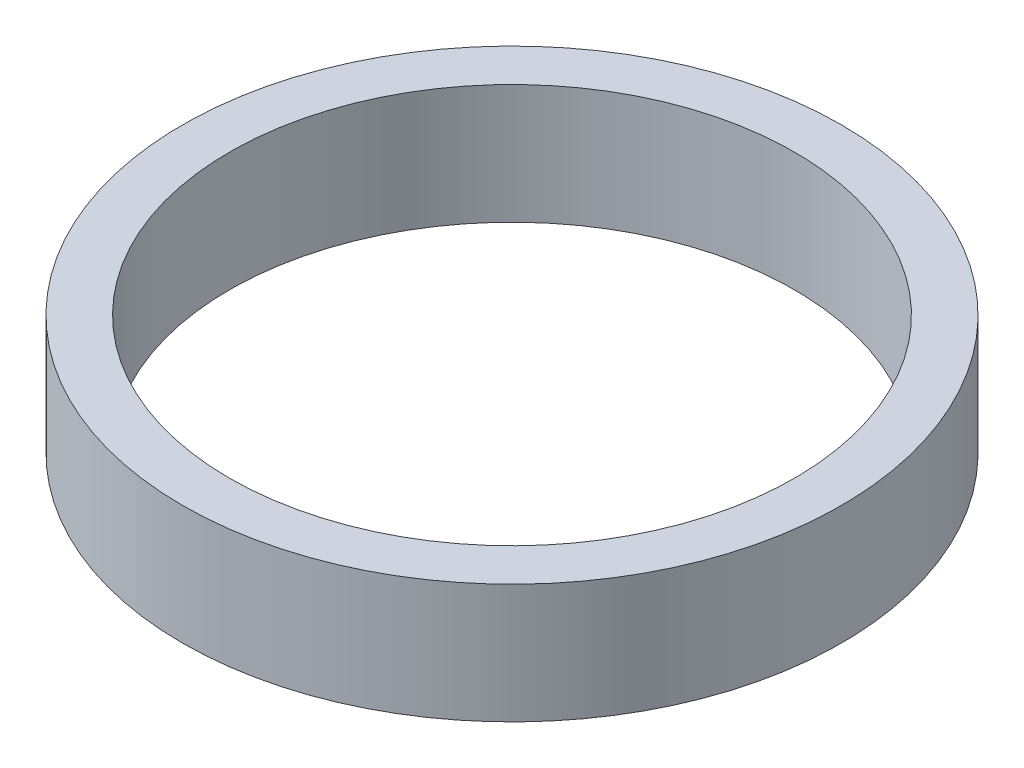
SolidWorks part; units mm, degrees
ref_plane "Front Plane" through (0, 0, 0) normal (0, 0, 1) x (1, 0, 0)
ref_plane "Top Plane" through (0, 0, 0) normal (0, 1, 0) x (1, 0, 0)
ref_plane "Right Plane" through (0, 0, 0) normal (1, 0, 0) x (0, 0, -1)
sketch "Sketch1" plane through (0, 0, 0) normal (0, 1, 0) x (1, 0, 0)
  circle A0 centre (0, 0) radius 52.5
  dimension "FLANGE_OD" = 105
extrude "Boss-Extrude1" add sketch "Sketch1" along normal blind 19
sketch "Sketch2" plane through (0, 0, 0) normal (0, 1, 0) x (1, 0, 0)
  circle A0 centre (0, 0) radius 45
  dimension "BORE_D" = 90
extrude "Cut-Extrude1" cut sketch "Sketch2" along normal through all
sketch "Sketch3" plane through (0, 19, 0) normal (0, 1, 0) x (1, 0, 0)
  circle A0 centre (0, 0) radius 24.4007 construction
  circle A1 centre (-24.4007, 0) radius 1.5
  dimension "BOLT_D" = 3
  dimension "BOLT_PCD" = 48.8014
extrude "Cut-Extrude2" cut sketch "Sketch3" against normal blind 13.1651 rebuild error yes
pattern_circular "CirPattern1" count 3 over 360 rebuild error yes
